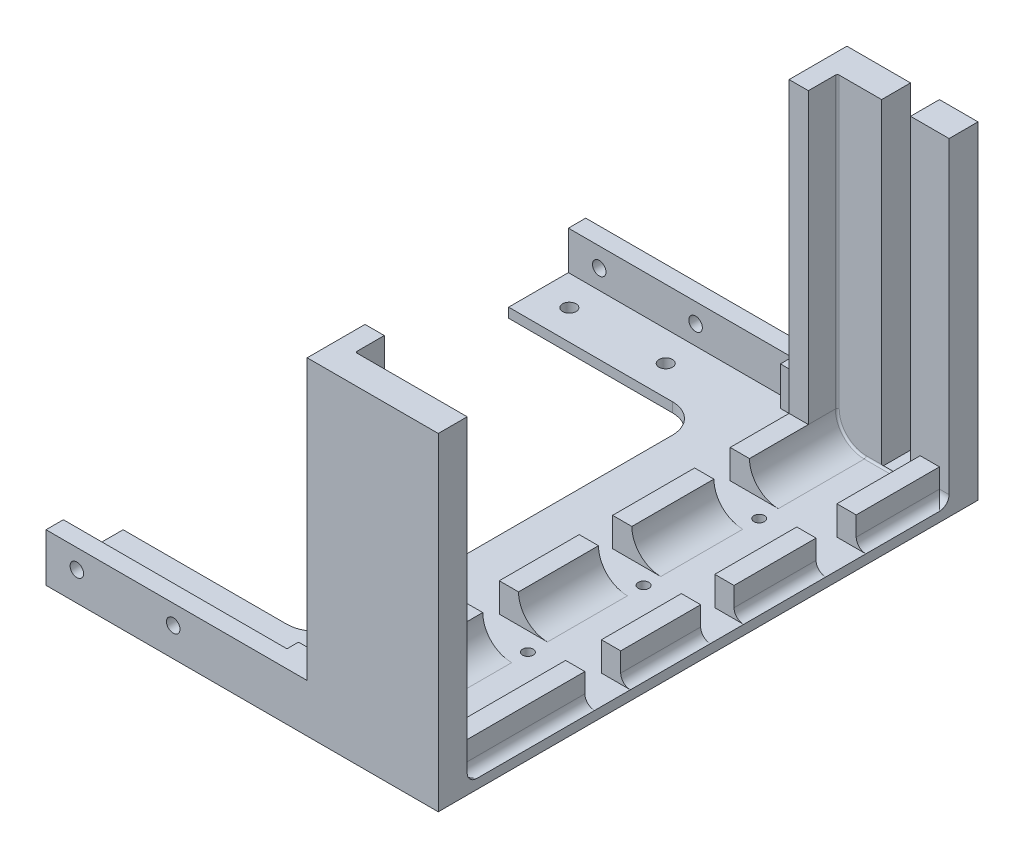
SolidWorks part; units mm, degrees
ref_plane "Front Plane" through (0, 0, 0) normal (0, 0, 1) x (1, 0, 0)
ref_plane "Top Plane" through (0, 0, 0) normal (0, 1, 0) x (1, 0, 0)
ref_plane "Right Plane" through (0, 0, 0) normal (1, 0, 0) x (0, 0, -1)
sketch "profile" plane through (0, 0, 0) normal (0, 0, 1) x (1, 0, 0)
  line L0 (11.8803, 7.4874) -> (14.5, 7.4874)
  line L1 (-5.5, 6.9749) -> (-7.8749, 4.6)
  line L2 (-7.8749, 4.6) -> (-12.1251, 4.6)
  line L3 (-12.1251, 4.6) -> (-14.5, 6.9749)
  line L4 (-8.1197, 7.4874) -> (-5.5, 7.4874)
  line L5 (-14.5, 6.9749) -> (-15.0126, 7.4874)
  line L6 (14.5, 6.9749) -> (12.1251, 4.6)
  line L7 (12.1251, 4.6) -> (7.8749, 4.6)
  line L8 (7.8749, 4.6) -> (5.5, 6.9749)
  line L9 (-14.7464, 10.3536) -> (-5.2536, 10.3536)
  line L10 (-14.5, 7.4874) -> (-11.8803, 7.4874)
  line L11 (5.5, 7.4874) -> (8.5334, 7.4874)
  line L12 (5.6673, 10.3536) -> (14.7464, 10.3536)
  line L13 (-15.0126, 7.4874) -> (-14.5, 7.4874)
  line L14 (-5.5, 6.9749) -> (-4.9874, 7.4874)
  line L15 (-4.9874, 7.4874) -> (-5.5, 7.4874)
  line L16 (5.5, 6.9749) -> (4.9874, 7.4874)
  line L17 (4.9874, 7.4874) -> (5.5, 7.4874)
  line L18 (14.5, 6.9749) -> (15.0126, 7.4874)
  line L19 (15.0126, 7.4874) -> (14.5, 7.4874)
  line L20 (-12.7464, 8.3536) -> (-14.7464, 10.3536)
  line L21 (-5.2536, 10.3536) -> (-7.2536, 8.3536)
  line L22 (7.6673, 8.3536) -> (5.6673, 10.3536)
  line L23 (14.7464, 10.3536) -> (12.7464, 8.3536)
  line L24 (-12.7464, 8.3536) -> (-11.8803, 7.4874)
  line L25 (-7.2536, 8.3536) -> (-8.1197, 7.4874)
  line L26 (7.6673, 8.3536) -> (8.5334, 7.4874)
  line L27 (12.7464, 8.3536) -> (11.8803, 7.4874)
  line L28 (-14.7464, 10.3536) -> (-20, 10.3536)
  line L29 (-20, 10.3536) -> (-20, 15.3536)
  line L30 (-20, 15.3536) -> (20, 15.3536)
  line L31 (20, 15.3536) -> (20, 10.3536)
  line L32 (20, 10.3536) -> (14.7464, 10.3536)
  line L33 (-5.2536, 10.3536) -> (5.6673, 10.3536)
  point P0 (-10, 4.6)
  point P1 (10, 4.6)
  dimension "D1" = 4.2503
  dimension "D2" = 5.7536
  dimension "D3" = 15.7497
  dimension "D4" = 20
  dimension "D5" = 5
extrude "Boss-Extrude1" add sketch "profile" along normal blind 250 contours L9 L33 L12 L32 L31 L30 L29 L28 region at (0, 12.8536, 0)
extrude "Boss-Extrude2" add sketch "Sketch1<3>" along normal blind 50 separate body contours L25 L21 L9 L20 L24 L10 L13 L5 L3 L2 L1 L14 L15 L4 | L27 L23 L12 L22 L26 L11 L17 L16 L8 L7 L6 L18 L19 L0 region at (10.0959, 7.5838, 0) region at (-10, 7.6238, 0)
sketch "Sketch1<3>" plane through (0, 0, 0) normal (0, 0, 1) x (1, 0, 0) same geometry as "profile"
pattern_linear "LPattern1" count 4 spacing 60 along (0, 0, 1) of "Boss-Extrude2"
sketch "Sketch2" plane through (0, 10.3536, 0) normal (0, -1, 0) x (1, 0, 0)
  line L0 (10, 250) -> (10, 0) construction
  line L1 (-20, 250) -> (20, 250) construction
  line L2 (12.1251, 0) -> (7.8749, 0) construction
  line L3 (-10, 230) -> (-10, 0) construction
  line L4 (-7.8749, 230) -> (-12.1251, 230) construction
  line L5 (-7.8749, 0) -> (-12.1251, 0) construction
  line L6 (-7.8749, 180) -> (-7.8749, 170) construction
  line L7 (-7.8749, 180) -> (-12.1251, 180) construction
  circle A0 centre (-10, 175) radius 2.75
  circle A1 centre (10, 175) radius 2.75
  circle A2 centre (-10, 115) radius 2.75
  circle A3 centre (10, 115) radius 2.75
  circle A4 centre (-10, 55) radius 2.75
  circle A5 centre (10, 55) radius 2.75
  point P21 (-7.8749, 175)
  dimension "D1" = 5.5
  dimension "D2" = 3
extrude "Cut-Extrude1" cut sketch "Sketch2" against normal through all
sketch "upper_acrylic_supp" plane through (0, 15.3536, 0) normal (0, 1, 0) x (1, 0, 0)
  line L0 (-20, 0) -> (20, 0) construction
  line L1 (-20, -250) -> (-34.5, -250) construction
  line L2 (-20, -250) -> (-20, 0) construction
  line L3 (-20, 0) -> (-34.5, 0) construction
  line L4 (-34.5, -250) -> (-34.5, 0) construction
  line L6 (-34.5, -250) -> (-24.5, -250)
  line L7 (-34.5, -250) -> (-34.5, -183.9264)
  line L8 (-34.5, -183.9264) -> (-24.5, -183.9264)
  line L9 (-24.5, -250) -> (-24.5, -183.9264)
  line L10 (-34.5, -165.3527) -> (-24.5, -165.3527)
  line L11 (-34.5, -165.3527) -> (-34.5, -123.8775)
  line L12 (-34.5, -123.8775) -> (-24.5, -123.8775)
  line L13 (-24.5, -165.3527) -> (-24.5, -123.8775)
  line L14 (-34.5, -106.5661) -> (-24.5, -106.5661)
  line L15 (-34.5, -106.5661) -> (-34.5, -64.0089)
  line L16 (-34.5, -64.0089) -> (-24.5, -64.0089)
  line L17 (-24.5, -106.5661) -> (-24.5, -64.0089)
  line L18 (-34.5, -45.5583) -> (-24.5, -45.5583)
  line L19 (-34.5, -45.5583) -> (-34.5, 0)
  line L20 (-34.5, 0) -> (-24.5, 0)
  line L21 (-24.5, -45.5583) -> (-24.5, 0)
  line L22 (-20, -250) -> (-40, -250)
  line L23 (-20, -250) -> (-20, 0)
  line L24 (-20, 0) -> (-40, 0)
  line L25 (-40, -250) -> (-40, 0)
  line M21 (-20, 0) -> (-20, -250)
  dimension "D1" = 5.5
  dimension "D2" = 10
  dimension "D3" = 20
extrude "Boss-Extrude3" add sketch "upper_acrylic_supp" against normal blind 5 contours L25 L22 L24 L21 L18 L19 L17 L14 L15 L16 L13 L10 L11 L12 L9 L6 L7 L8 M21 | L14 L17 L16 L15 | L10 L13 L12 L11 | L6 L9 L8 L7 | L18 L21 L20 L19 region at (-29.5, 15.3536, 216.9632) region at (-30.3215, 15.3536, 123.2164) region at (-29.5, 15.3536, 22.7792) region at (-29.5, 15.3536, 144.6151) region at (-29.5, 15.3536, 85.2875)
extrude "Boss-Extrude4" add sketch "upper_acrylic_supp<3>" along normal blind 15 contours L6 L9 L8 L7 | L10 L13 L12 L11 | L14 L17 L16 L15 | L18 L21 L20 L19 region at (-29.5, 15.3536, 216.9632) region at (-29.5, 15.3536, 22.7792) region at (-29.5, 15.3536, 144.6151) region at (-29.5, 15.3536, 85.2875)
sketch "upper_acrylic_supp<3>" plane through (0, 15.3536, 0) normal (0, 1, 0) x (1, 0, 0) same geometry as "upper_acrylic_supp"
fillet "Fillet1" radius 15 4 edges at (-24.5, 15.3536, 22.7792) (-24.5, 15.3536, 85.2875) (-24.5, 15.3536, 144.6151) (-24.5, 15.3536, 216.9632)
sketch "Sketch4" plane through (0, 15.3536, 0) normal (0, 1, 0) x (1, 0, 0)
  line L0 (20, -250) -> (20, 0) construction
  line L1 (-40, -250) -> (20, -250)
  line L2 (-40, -250) -> (-40, -265)
  line L3 (-40, -265) -> (20, -265)
  line L4 (20, -250) -> (20, -265)
  line L5 (-40, 0) -> (20, 0)
  line L6 (-40, 0) -> (-40, 15)
  line L7 (-40, 15) -> (20, 15)
  line L8 (20, 0) -> (20, 15)
  line L10 (-34.5, -265) -> (-34.5, 15) construction
  dimension "D1" = 15
  dimension "D2" = 15
extrude "Boss-Extrude5" add sketch "Sketch4" along normal mid plane 10
extrude "Boss-Extrude6" add sketch "Sketch4<3>" along normal blind 60
sketch "Sketch4<3>" plane through (0, 15.3536, 0) normal (0, 1, 0) x (1, 0, 0) same geometry as "Sketch4"
sketch "Sketch5" plane through (0, 0, 250) normal (0, 0, -1) x (-1, 0, 0)
  line L0 (-20, 75.3536) -> (40, 75.3536) construction
  line L1 (40, 15.3536) -> (34.5, 15.3536)
  line L2 (40, 15.3536) -> (40, 75.3536)
  line L3 (40, 75.3536) -> (34.5, 75.3536)
  line L4 (34.5, 15.3536) -> (34.5, 75.3536)
  line L6 (34.5, 15.3536) -> (24.5, 15.3536)
  line L7 (34.5, 15.3536) -> (34.5, 75.3536)
  line L8 (34.5, 75.3536) -> (24.5, 75.3536)
  line L9 (24.5, 15.3536) -> (24.5, 75.3536)
  line M5 (40, 75.3536) -> (-20, 75.3536)
  line M9 (24.5, 30.3536) -> (34.5, 30.3536)
  dimension "D1" = 5.5
  dimension "D2" = 10
extrude "Boss-Extrude7" add sketch "Sketch5" along normal blind 15 contours L9 L4 M9 M5 region at (-29.5, 52.8536, 250)
extrude "Boss-Extrude8" add sketch "Sketch5<3>" against normal blind 15 from surface contours L9 L4 M9 M5 region at (-29.5, 52.8536, 250) starting at face at (-18.2633, 33.7152, 0)
sketch "Sketch5<3>" plane through (0, 0, 250) normal (0, 0, -1) x (-1, 0, 0) same geometry as "Sketch5"
fillet "Fillet2" radius 1 6 edges at (5.25, 15.3536, 0) (-20.1066, 19.747, 0) (5.25, 15.3536, 250) (-20.1066, 19.747, 250) (-24.5, 52.8536, 0) (-24.5, 52.8536, 250)
sketch "Sketch6" plane through (-40, 0, 0) normal (-1, 0, 0) x (0, 0, 1)
  line L1 (250, 15.3536) -> (256, 15.3536)
  line L2 (250, 15.3536) -> (250, 75.3536)
  line L3 (250, 75.3536) -> (256, 75.3536)
  line L4 (256, 15.3536) -> (256, 75.3536)
  line L6 (0, 15.3536) -> (-6, 15.3536)
  line L7 (0, 15.3536) -> (0, 75.3536)
  line L8 (0, 75.3536) -> (-6, 75.3536)
  line L9 (-6, 15.3536) -> (-6, 75.3536)
  dimension "D1" = 6
  dimension "D2" = 6
extrude "Cut-Extrude2" cut sketch "Sketch6" against normal blind 6
sketch "Sketch7" plane through (-40, 0, 0) normal (-1, 0, 0) x (0, 0, 1)
  line L8 (265, 75.3536) -> (256, 75.3536)
  line L9 (256, 75.3536) -> (256, 15.3536)
  line L10 (256, 15.3536) -> (-6, 15.3536)
  line L11 (-6, 15.3536) -> (-6, 75.3536)
  line L12 (-6, 75.3536) -> (-15, 75.3536)
  line L13 (-15, 75.3536) -> (-15, 10.3536)
  line L14 (-15, 10.3536) -> (265, 10.3536)
  line L15 (265, 10.3536) -> (265, 75.3536)
  line L16 (265, 75.3536) -> (256, 75.3536)
  line L17 (256, 75.3536) -> (256, 15.3536)
  line L18 (256, 15.3536) -> (-6, 15.3536)
  line L19 (-6, 15.3536) -> (-6, 75.3536)
  line L20 (-6, 75.3536) -> (-15, 75.3536)
  line L21 (-15, 75.3536) -> (-15, 10.3536)
  line L22 (-15, 10.3536) -> (265, 10.3536)
  line L23 (265, 10.3536) -> (265, 75.3536)
  dimension "D1" = 0
extrude "Boss-Extrude9" add sketch "Sketch7" along normal blind 30
sketch "Sketch8" plane through (-70, 0, 0) normal (-1, 0, 0) x (0, 0, 1)
  line L0 (-15, 10.3536) -> (265, 10.3536) construction
  line L1 (-44.3745, 35.3536) -> (289.2282, 35.3536)
  line L2 (-44.3745, 35.3536) -> (-44.3745, 94.3849)
  line L3 (-44.3745, 94.3849) -> (289.2282, 94.3849)
  line L4 (289.2282, 35.3536) -> (289.2282, 94.3849)
  dimension "D1" = 25
extrude "Cut-Extrude3" cut sketch "Sketch8" against normal blind 150
sketch "Sketch9" plane through (-34, 0, 0) normal (-1, 0, 0) x (0, 0, 1)
  line L4 (256, 15.3536) -> (256, 35.3536)
  line L5 (256, 35.3536) -> (250, 35.3536)
  line L6 (250, 35.3536) -> (250, 15.3536)
  line L7 (250, 15.3536) -> (256, 15.3536)
  line L8 (256, 15.3536) -> (256, 35.3536)
  line L9 (256, 35.3536) -> (250, 35.3536)
  line L10 (250, 35.3536) -> (250, 15.3536)
  line L11 (250, 15.3536) -> (256, 15.3536)
  line L12 (0, 35.3536) -> (-6, 35.3536)
  line L13 (-6, 35.3536) -> (-6, 15.3536)
  line L14 (-6, 15.3536) -> (0, 15.3536)
  line L15 (0, 15.3536) -> (0, 35.3536)
  line L16 (0, 35.3536) -> (-6, 35.3536)
  line L17 (-6, 35.3536) -> (-6, 15.3536)
  line L18 (-6, 15.3536) -> (0, 15.3536)
  line L19 (0, 15.3536) -> (0, 35.3536)
  dimension "D1" = 0
  dimension "D2" = 0
extrude "cloth_escape_gap" add sketch "Sketch9" along normal blind 20
sketch "Sketch11" plane through (-70, 0, 0) normal (-1, 0, 0) x (0, 0, 1)
  line L0 (256, 35.3536) -> (256, 15.3536) construction
  line L1 (-15, 35.3536) -> (-6, 35.3536)
  line L2 (-15, 35.3536) -> (-15, 15.3536)
  line L3 (-15, 15.3536) -> (-6, 15.3536)
  line L4 (-6, 35.3536) -> (-6, 15.3536)
  line L5 (265, 35.3536) -> (256, 35.3536)
  line L6 (265, 35.3536) -> (265, 15.3536)
  line L7 (265, 15.3536) -> (256, 15.3536)
  line L8 (256, 35.3536) -> (256, 15.3536)
  line L9 (256, 15.3536) -> (256, 35.3536) construction
extrude "Boss-Extrude11" add sketch "Sketch11" along normal blind 100
sketch "Sketch12" plane through (0, 10.3536, 0) normal (0, -1, 0) x (1, 0, 0)
  line L0 (-70, -15) -> (-170, -10.5)
  line L1 (-170, -15) -> (-170, -6) construction
  line L2 (-170, -10.5) -> (-170, -15)
  line L3 (-170, -15) -> (-70, -15) construction
  line L4 (-170, -15) -> (-70, -15)
  line L5 (-70, 265) -> (-170, 260.5)
  line L6 (-170, 256) -> (-170, 265) construction
  line L7 (-170, 260.5) -> (-170, 265)
  line L8 (-170, 265) -> (-70, 265)
extrude "Cut-Extrude4" cut sketch "Sketch12" against normal blind 68 contours L8 L7 L5 | L0 L2 L4 region at (-136.6667, 10.3536, 263.5)
sketch "Sketch13" plane through (-70, 0, 0) normal (-1, 0, 0) x (0, 0, 1)
  line L0 (256, 15.3536) -> (265, 15.3536) construction
  line L1 (-15, 10.3536) -> (25, 10.3536)
  line L2 (-15, 10.3536) -> (-15, 15.3536)
  line L3 (-15, 15.3536) -> (25, 15.3536)
  line L4 (25, 10.3536) -> (25, 15.3536)
  line L5 (265, 10.3536) -> (225, 10.3536)
  line L6 (265, 10.3536) -> (265, 15.3536)
  line L7 (265, 15.3536) -> (225, 15.3536)
  line L8 (225, 10.3536) -> (225, 15.3536)
  line L9 (256, 15.3536) -> (-6, 15.3536) construction
  dimension "D1" = 40
  dimension "D2" = 40
extrude "Boss-Extrude13" add sketch "Sketch13" along normal blind 100
sketch "Sketch14" plane through (0, 15.3536, 0) normal (0, 1, 0) x (1, 0, 0)
  line L3 (-70, -265) -> (-170, -260.5)
  line L4 (-170, -260.5) -> (-170, -265)
  line L5 (-170, -265) -> (-70, -265)
  line L6 (-70, -265) -> (-170, -260.5)
  line L7 (-170, -260.5) -> (-170, -265)
  line L8 (-170, -265) -> (-70, -265)
  line L9 (-170, 15) -> (-170, 10.5)
  line L10 (-170, 10.5) -> (-70, 15)
  line L11 (-70, 15) -> (-170, 15)
  line L12 (-170, 15) -> (-170, 10.5)
  line L13 (-170, 10.5) -> (-70, 15)
  line L14 (-70, 15) -> (-170, 15)
  dimension "D1" = 0
  dimension "D2" = 0
extrude "Cut-Extrude5" cut sketch "Sketch14" against normal blind 100
fillet "Fillet3" radius 15 2 edges at (-70, 12.8536, 25) (-70, 12.8536, 225)
sketch "Sketch16" plane through (0, 15.3536, 0) normal (0, 1, 0) x (1, 0, 0)
  line L0 (20, -1) -> (-9.5, -1) construction
  line L1 (-34.5, -235) -> (18.5, -235) construction
  line L2 (-34.5, -235) -> (-34.5, -1) construction
  line L3 (-34.5, -1) -> (18.5, -1) construction
  line L4 (18.5, -235) -> (18.5, -1) construction
  line L5 (20, -265) -> (-70, -265) construction
  line L6 (18.5, -265) -> (33.5, -265)
  line L7 (18.5, -265) -> (18.5, 15)
  line L8 (18.5, 15) -> (33.5, 15)
  line L9 (33.5, -265) -> (33.5, 15)
  line L10 (-70, 15) -> (20, 15) construction
  line L11 (18.5, -250) -> (33.5, -250)
  line L12 (18.5, 0) -> (33.5, 0)
  line L13 (-23.5, -250) -> (20, -250) construction
  line L14 (-9.5, 0) -> (20, 0) construction
  line L15 (18.5, -250) -> (28.5, -250)
  line L16 (28.5, -250) -> (28.5, -183.9264)
  line L17 (28.5, 0) -> (18.5, 0)
  line L18 (18.5, -183.9264) -> (28.5, -183.9264)
  line L19 (18.5, -165.3527) -> (28.5, -165.3527)
  line L20 (18.5, -123.8775) -> (28.5, -123.8775)
  line L21 (18.5, -106.5661) -> (28.5, -106.5661)
  line L22 (18.5, -64.0089) -> (28.5, -64.0089)
  line L23 (18.5, -43.1778) -> (28.5, -43.1778)
  line L24 (-34.5, -165.3527) -> (-9.5, -165.3527) construction
  line L25 (-34.5, -183.9264) -> (-9.5, -183.9264) construction
  line L26 (-34.5, -106.5661) -> (-9.5, -106.5661) construction
  line L27 (-34.5, -123.8775) -> (-9.5, -123.8775) construction
  line L28 (-9.5, -64.0089) -> (-24.5, -64.0089) construction
  line L30 (28.5, -165.3527) -> (28.5, -123.8775)
  line L31 (28.5, -106.5661) -> (28.5, -64.0089)
  line L32 (28.5, -43.1778) -> (28.5, 0)
  line M38 (-9.5, -249) -> (20, -249)
  line M39 (20, -249) -> (20, -1)
  line M40 (20, -1) -> (-9.5, -1)
  dimension "D1" = 53
  dimension "D2" = 15
  dimension "D3" = 10
extrude "Boss-Extrude14" add sketch "Sketch16" along direction (0, -1, 0) on the side of the normal up to surface (20 mm away) from surface contours L7 L12 L9 L8 | L11 L7 L6 L9 region at (26, 15.3536, 257.5) region at (26, 15.3536, -7.5) up to face at (-51.6423, 35.3536, 251.8089) starting at face at (-10, 10.3536, 25)
extrude "Cut-Extrude6" cut sketch "Sketch16<5>" against normal blind 10 and the other way blind 30 contours L11 L7 L6 L9 | L32 L23 L22 L31 L21 L20 L30 L19 L18 L16 L11 L9 L12 M39 | L19 L30 L20 M39 | L21 L31 L22 M39 | L23 L32 L12 L7 M40 M39 | L7 L12 L9 L8 | L7 L23 M39 M40 | L23 L7 L22 M39 | L22 L7 L21 M39 | L21 L7 L20 M39 | L20 L7 L19 M39 | L19 L7 L18 M39 | L18 L7 M38 M39 | L18 L7 L11 L16 M39 M38 region at (26, 15.3536, 257.5) region at (24.2367, 15.3536, 217.0499) region at (29.1213, 15.3536, 121.3942) region at (19.25, 15.3536, 216.4632) region at (26, 15.3536, -7.5) region at (19.25, 15.3536, 174.6396) region at (24.2296, 15.3536, 21.5031) region at (19.25, 15.3536, 144.6151) region at (19.25, 15.3536, 115.2218) region at (24.25, 15.3536, 144.6151) region at (19.25, 15.3536, 22.0889) region at (19.25, 15.3536, 53.5934) region at (19.25, 15.3536, 85.2875) region at (24.25, 15.3536, 85.2875)
sketch "Sketch16<5>" plane through (0, 15.3536, 0) normal (0, 1, 0) x (1, 0, 0) same geometry as "Sketch16"
extrude "Boss-Extrude15" add sketch "Sketch16<6>" against normal up to surface (5 mm away) contours L32 L23 L22 L31 L21 L20 L30 L19 L18 L16 L11 L9 L12 M39 | L18 L7 L11 L16 M39 M38 | L11 L7 L6 L9 | L19 L30 L20 M39 | L21 L31 L22 M39 | L23 L32 L12 L7 M40 M39 | L7 L12 L9 L8 | L7 L23 M39 M40 | L23 L7 L22 M39 | L22 L7 L21 M39 | L21 L7 L20 M39 | L20 L7 L19 M39 | L19 L7 L18 M39 | L18 L7 M38 M39 region at (26, 15.3536, 257.5) region at (24.2367, 15.3536, 217.0499) region at (29.1213, 15.3536, 121.3942) region at (19.25, 15.3536, 216.4632) region at (26, 15.3536, -7.5) region at (19.25, 15.3536, 174.6396) region at (24.2296, 15.3536, 21.5031) region at (19.25, 15.3536, 144.6151) region at (19.25, 15.3536, 115.2218) region at (24.25, 15.3536, 144.6151) region at (19.25, 15.3536, 22.0889) region at (19.25, 15.3536, 53.5934) region at (19.25, 15.3536, 85.2875) region at (24.25, 15.3536, 85.2875) up to face at (-90.5656, 10.3536, 125)
sketch "Sketch16<6>" plane through (0, 15.3536, 0) normal (0, 1, 0) x (1, 0, 0) same geometry as "Sketch16"
extrude "Boss-Extrude16" add sketch "Sketch16<7>" along normal up to surface (20 mm away) contours L11 L7 L6 L9 | L7 L12 L9 L8 region at (26, 15.3536, 257.5) region at (26, 15.3536, -7.5) up to face at (-51.8923, 35.3536, 251.8089)
sketch "Sketch16<7>" plane through (0, 15.3536, 0) normal (0, 1, 0) x (1, 0, 0) same geometry as "Sketch16"
extrude "Boss-Extrude17" add sketch "Sketch16<8>" along normal up to surface (15 mm away) contours L18 L7 L11 L16 M39 M38 | L19 L30 L20 M39 | L21 L31 L22 M39 | L23 L32 L12 L7 M40 M39 | L7 L23 M39 M40 | L22 L7 L21 M39 | L20 L7 L19 M39 | L18 L7 M38 M39 region at (24.2367, 15.3536, 217.0499) region at (19.25, 15.3536, 216.4632) region at (24.2296, 15.3536, 21.5031) region at (19.25, 15.3536, 144.6151) region at (24.25, 15.3536, 144.6151) region at (19.25, 15.3536, 22.0889) region at (19.25, 15.3536, 85.2875) region at (24.25, 15.3536, 85.2875) up to face at (-29.5, 30.3536, 209.4632)
sketch "Sketch16<8>" plane through (0, 15.3536, 0) normal (0, 1, 0) x (1, 0, 0) same geometry as "Sketch16"
extrude "Boss-Extrude18" add sketch "Sketch14<2>" along normal up to surface (20 mm away) and the other way up to surface (5 mm away) up to face at (-49.3923, 35.3536, -1.8089) other way up to face at (-88.0656, 10.3536, 125)
sketch "Sketch14<2>" plane through (0, 15.3536, 0) normal (0, 1, 0) x (1, 0, 0) same geometry as "Sketch14"
fillet "Fillet4" radius 5 6 edges at (31, 15.3536, 250) (31, 15.3536, 0) (28.5, 15.3536, 21.5889) (28.5, 15.3536, 85.2875) (28.5, 15.3536, 144.6151) (28.5, 15.3536, 216.9632)
sketch "Sketch18" plane through (0, 35.3536, 0) normal (0, 1, 0) x (1, 0, 0)
  line L2 (-34.5, -250) -> (-34.5, -265)
  line L3 (-34.5, 15) -> (-34.5, 0)
  line L12 (-23.5, 0) -> (33.5, 0)
  line L13 (33.5, 0) -> (33.5, 15)
  line L14 (33.5, 15) -> (-170, 15)
  line L15 (-170, 15) -> (-170, 6)
  line L30 (-170, 6) -> (-54, 6)
  line L32 (-54, 6) -> (-54, 0)
  line L38 (-54, 0) -> (-34.5, 0)
  line L39 (-34.5, 0) -> (-34.5, -15)
  line L50 (-34.5, -15) -> (-24.5, -15)
  line L51 (-24.5, -15) -> (-24.5, -1)
  line L52 (-23.5, 0) -> (33.5, 0)
  line L53 (33.5, 0) -> (33.5, 15)
  line L54 (33.5, 15) -> (-34.5, 15)
  line L59 (-34.5, 0) -> (-34.5, -15)
  line L60 (-34.5, -15) -> (-24.5, -15)
  line L61 (-24.5, -15) -> (-24.5, -1)
  line L62 (-170, -265) -> (33.5, -265)
  line L63 (33.5, -265) -> (33.5, -250)
  line L64 (33.5, -250) -> (-23.5, -250)
  line L65 (-24.5, -249) -> (-24.5, -235)
  line L66 (-24.5, -235) -> (-34.5, -235)
  line L67 (-34.5, -235) -> (-34.5, -250)
  line L68 (-34.5, -250) -> (-54, -250)
  line L69 (-54, -250) -> (-54, -256)
  line L70 (-54, -256) -> (-170, -256)
  line L71 (-170, -256) -> (-170, -265)
  line L72 (-34.5, -265) -> (33.5, -265)
  line L73 (33.5, -265) -> (33.5, -250)
  line L74 (33.5, -250) -> (-23.5, -250)
  line L75 (-24.5, -249) -> (-24.5, -235)
  line L76 (-24.5, -235) -> (-34.5, -235)
  line L77 (-34.5, -235) -> (-34.5, -250)
  arc A5 (-23.5, 0) -> (-24.5, -1) centre (-23.5, -1) ccw
  arc A6 (-23.5, 0) -> (-24.5, -1) centre (-23.5, -1) ccw
  arc A7 (-24.5, -249) -> (-23.5, -250) centre (-23.5, -249) ccw
  arc A8 (-24.5, -249) -> (-23.5, -250) centre (-23.5, -249) ccw
  dimension "D1" = 0
  dimension "D2" = 0
extrude "Boss-Extrude21" add sketch "Sketch18" along normal blind 170 from surface starting at face at (-91.6787, 10.3536, 125)
sketch "Sketch19" plane through (0, 15.3536, 0) normal (0, 1, 0) x (1, 0, 0)
  line L0 (-170, -25) -> (-170, 6) construction
  line L1 (-70, -125) -> (-196.5165, -125) construction
  line L2 (-70, -210) -> (-70, -40) construction
  circle A0 centre (-154, -9.5) radius 3.5
  circle A1 centre (-104, -9.5) radius 3.5
  circle A2 centre (-104, -240.5) radius 3.5
  circle A3 centre (-154, -240.5) radius 3.5
  point P6 (-170, -9.5)
  dimension "D1" = 7
  dimension "D2" = 50
  dimension "D3" = 50
extrude "Cut-Extrude7" cut sketch "Sketch19" against normal blind 10
sketch "Sketch20" plane through (0, 0, 256) normal (0, 0, -1) x (-1, 0, 0)
  line L4 (34.5, 35.3536) -> (34.5, 15.3536)
  line L5 (34.5, 15.3536) -> (54, 15.3536)
  line L6 (54, 15.3536) -> (54, 35.3536)
  line L7 (54, 35.3536) -> (34.5, 35.3536)
  line L8 (34.5, 35.3536) -> (34.5, 15.3536)
  line L9 (34.5, 15.3536) -> (54, 15.3536)
  line L10 (54, 15.3536) -> (54, 35.3536)
  line L11 (54, 35.3536) -> (34.5, 35.3536)
  circle A0 centre (104, 25.3536) radius 3.5
  circle A1 centre (154, 25.3536) radius 3.5
  point P8 (54, 25.3536)
  dimension "D3" = 7
  dimension "D2" = 50
  dimension "D4" = 50
  dimension "D1" = 0
extrude "Cut-Extrude8" cut sketch "Sketch20" against normal blind 10 and the other way blind 355 contours A0 | A1 region at (-104, 25.3536, 256) region at (-154, 25.3536, 256)
sketch "Sketch21" plane through (0, 0, 0) normal (0, 0, 1) x (1, 0, 0)
  line L1 (13.5, 15.3536) -> (-1.5, 15.3536)
  line L2 (13.5, 15.3536) -> (13.5, 212.8546)
  line L3 (13.5, 212.8546) -> (-1.5, 212.8546)
  line L4 (-1.5, 15.3536) -> (-1.5, 212.8546)
  line L6 (18.5, 15.3536) -> (-9.5, 15.3536) construction
  line L7 (18.5, 30.3536) -> (18.5, 16.3536) construction
  dimension "D1" = 15
  dimension "D2" = 5
extrude "Cut-Extrude9" cut sketch "Sketch21" against normal blind 130
